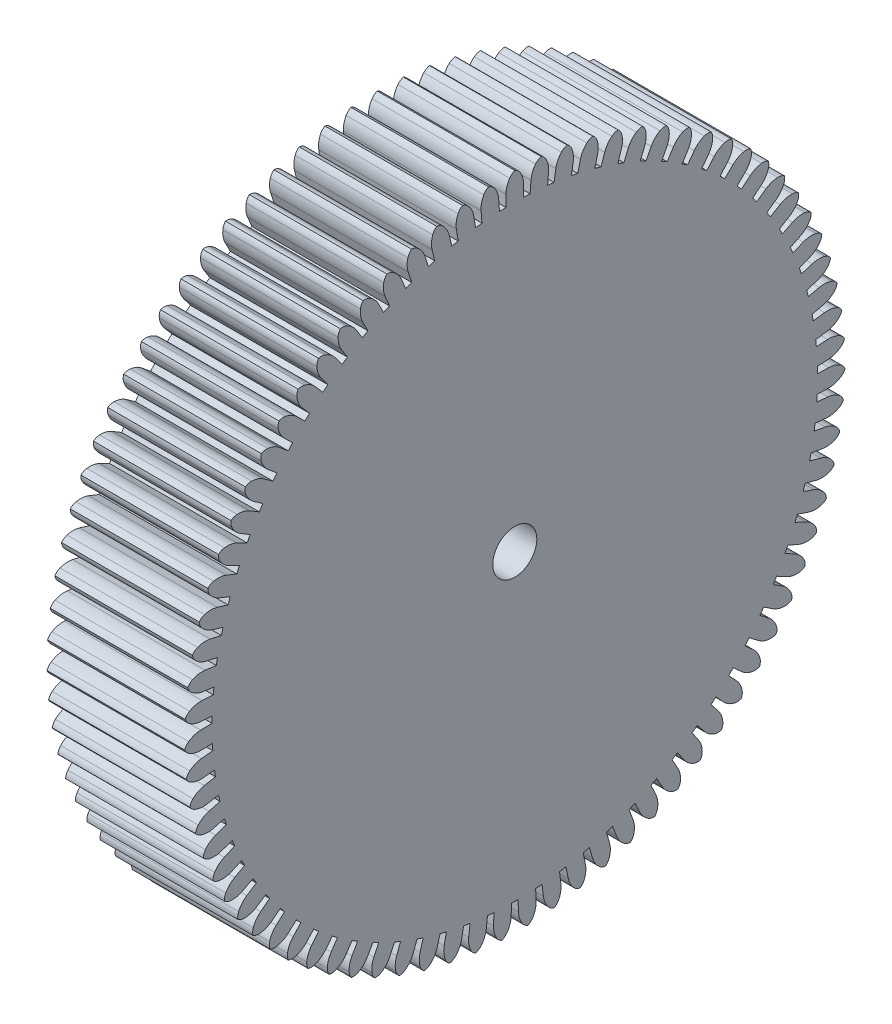
SolidWorks part; units mm, degrees
ref_plane "Front Plane" through (0, 0, 0) normal (0, 0, 1) x (1, 0, 0)
ref_plane "Top Plane" through (0, 0, 0) normal (0, 1, 0) x (1, 0, 0)
ref_plane "Right Plane" through (0, 0, 0) normal (1, 0, 0) x (0, 0, -1)
sketch "Sketch1" plane through (0, 0, 0) normal (1, 0, 0) x (0, 0, -1)
  line L0 (-0.64, 21.9907) -> (-0.64, 22.8144)
  line L1 (0, 24) -> (0, 22)
  line L2 (0, 55) -> (0, -55) construction
  line L3 (0.64, 21.9907) -> (0.64, 22.8144)
  line L4 (2.3851, 21.8703) -> (2.4506, 22.6915)
  line L5 (1.1092, 21.972) -> (1.1746, 22.7932)
  line L6 (4.1152, 21.6117) -> (4.2457, 22.425)
  line L7 (2.8514, 21.8144) -> (2.9818, 22.6278)
  line L8 (5.8192, 21.2164) -> (6.0139, 22.0168)
  line L9 (4.5755, 21.5189) -> (4.7702, 22.3193)
  line L10 (7.4865, 20.687) -> (7.7442, 21.4694)
  line L11 (6.2707, 21.0874) -> (6.5284, 21.8698)
  line L12 (9.1064, 20.0268) -> (9.4254, 20.7863)
  line L13 (7.9263, 20.5225) -> (8.2453, 21.282)
  line L14 (10.6688, 19.24) -> (11.0471, 19.9717)
  line L15 (9.5318, 19.8279) -> (9.9101, 20.5596)
  line L16 (12.1637, 18.3315) -> (12.5989, 19.0309)
  line L17 (11.077, 19.0079) -> (11.5122, 19.7073)
  line L18 (13.5817, 17.3072) -> (14.0711, 17.9697)
  line L19 (12.5521, 18.0678) -> (13.0416, 18.7303)
  line L20 (14.9138, 16.1734) -> (15.4543, 16.795)
  line L21 (13.9479, 17.0134) -> (14.4885, 17.6349)
  line L22 (16.1516, 14.9374) -> (16.7398, 15.514)
  line L23 (15.2556, 15.8514) -> (15.8438, 16.4281)
  line L24 (17.2873, 13.6069) -> (17.9195, 14.135)
  line L25 (16.4667, 14.5893) -> (17.0989, 15.1174)
  line L26 (18.3138, 12.1904) -> (18.9859, 12.6666)
  line L27 (17.5738, 13.2349) -> (18.2459, 13.7111)
  line L28 (19.2244, 10.6969) -> (19.9323, 11.1181)
  line L29 (18.5698, 11.7968) -> (19.2776, 12.2181)
  line L30 (20.0135, 9.1357) -> (20.7526, 9.4994)
  line L31 (19.4483, 10.2841) -> (20.1874, 10.6478)
  line L32 (20.6761, 7.5167) -> (21.4417, 7.8206)
  line L33 (20.2039, 8.7064) -> (20.9696, 9.0103)
  line L34 (21.2079, 5.8502) -> (21.9953, 6.0923)
  line L35 (20.8318, 7.0737) -> (21.6191, 7.3158)
  line L36 (21.6057, 4.1468) -> (22.4098, 4.3255)
  line L37 (21.3279, 5.3963) -> (22.132, 5.575)
  line L38 (21.8668, 2.4171) -> (22.6826, 2.5314)
  line L39 (21.6892, 3.6847) -> (22.505, 3.799)
  line L40 (21.9897, 0.6721) -> (22.812, 0.7212)
  line L41 (21.9134, 1.9498) -> (22.7357, 1.9989)
  line L42 (21.9736, -1.0771) -> (22.7972, -1.0935)
  line L43 (21.9991, 0.2027) -> (22.8226, 0.1863)
  line L44 (21.8186, -2.8195) -> (22.6383, -2.9013)
  line L45 (21.9456, -1.5458) -> (22.7653, -1.6276)
  line L46 (21.5256, -4.5441) -> (22.3362, -4.6907)
  line L47 (21.7534, -3.2845) -> (22.564, -3.4311)
  line L48 (21.0965, -6.2399) -> (21.8929, -6.4505)
  line L49 (21.4237, -5.0024) -> (22.2201, -5.213)
  line L50 (20.5341, -7.8963) -> (21.3112, -8.1695)
  line L51 (20.9585, -6.6888) -> (21.7357, -6.9619)
  line L52 (19.8418, -9.5028) -> (20.5948, -9.8368)
  line L53 (20.3609, -8.3328) -> (21.1138, -8.6668)
  line L54 (19.0241, -11.0492) -> (19.7481, -11.442)
  line L55 (19.6345, -9.9241) -> (20.3585, -10.3169)
  line L56 (18.0861, -12.5257) -> (18.7766, -12.9748)
  line L57 (18.7839, -11.4527) -> (19.4745, -11.9018)
  line L58 (17.0337, -13.9231) -> (17.6864, -14.4256)
  line L59 (17.8146, -12.9089) -> (18.4673, -13.4114)
  line L60 (15.8737, -15.2324) -> (16.4844, -15.7852)
  line L61 (16.7327, -14.2834) -> (17.3434, -14.8363)
  line L62 (14.6133, -16.4454) -> (15.1781, -17.045)
  line L63 (15.545, -15.5677) -> (16.1098, -16.1673)
  line L64 (13.2605, -17.5545) -> (13.7759, -18.197)
  line L65 (14.259, -16.7535) -> (14.7744, -17.3961)
  line L66 (11.8239, -18.5525) -> (12.2866, -19.234)
  line L67 (12.8828, -17.8335) -> (13.3456, -18.5149)
  line L68 (10.3125, -19.4333) -> (10.7196, -20.1494)
  line L69 (11.4252, -18.8006) -> (11.8324, -19.5167)
  line L70 (8.7359, -20.1912) -> (9.0849, -20.9374)
  line L71 (9.8954, -19.6489) -> (10.2444, -20.3951)
  line L72 (7.1041, -20.8214) -> (7.3927, -21.593)
  line L73 (8.303, -20.373) -> (8.5916, -21.1446)
  line L74 (5.4274, -21.32) -> (5.6538, -22.1121)
  line L75 (6.6581, -20.9683) -> (6.8845, -21.7603)
  line L76 (3.7164, -21.6838) -> (3.8791, -22.4913)
  line L77 (4.9712, -21.431) -> (5.1339, -22.2385)
  line L78 (1.9818, -21.9106) -> (2.0799, -22.7284)
  line L79 (3.2527, -21.7582) -> (3.3508, -22.5761)
  line L80 (0.2348, -21.9987) -> (0.2675, -22.8218)
  line L81 (1.5138, -21.9479) -> (1.5465, -22.771)
  line L82 (-1.5138, -21.9479) -> (-1.5465, -22.771)
  line L83 (-0.2348, -21.9987) -> (-0.2675, -22.8218)
  line L84 (-3.2527, -21.7582) -> (-3.3508, -22.5761)
  line L85 (-1.9818, -21.9106) -> (-2.0799, -22.7284)
  line L86 (-4.9712, -21.431) -> (-5.1339, -22.2385)
  line L87 (-3.7164, -21.6838) -> (-3.8791, -22.4913)
  line L88 (-6.6581, -20.9683) -> (-6.8845, -21.7603)
  line L89 (-5.4274, -21.32) -> (-5.6538, -22.1121)
  line L90 (-8.303, -20.373) -> (-8.5916, -21.1446)
  line L91 (-7.1041, -20.8214) -> (-7.3927, -21.593)
  line L92 (-9.8954, -19.6489) -> (-10.2444, -20.3951)
  line L93 (-8.7359, -20.1912) -> (-9.0849, -20.9374)
  line L94 (-11.4252, -18.8006) -> (-11.8324, -19.5167)
  line L95 (-10.3125, -19.4333) -> (-10.7196, -20.1494)
  line L96 (-12.8828, -17.8335) -> (-13.3456, -18.5149)
  line L97 (-11.8239, -18.5525) -> (-12.2866, -19.234)
  line L98 (-14.259, -16.7535) -> (-14.7744, -17.3961)
  line L99 (-13.2605, -17.5545) -> (-13.7759, -18.197)
  line L100 (-15.545, -15.5677) -> (-16.1098, -16.1673)
  line L101 (-14.6133, -16.4454) -> (-15.1781, -17.045)
  line L102 (-16.7327, -14.2834) -> (-17.3434, -14.8363)
  line L103 (-15.8737, -15.2324) -> (-16.4844, -15.7852)
  line L104 (-17.8146, -12.9089) -> (-18.4673, -13.4114)
  line L105 (-17.0337, -13.9231) -> (-17.6864, -14.4256)
  line L106 (-18.7839, -11.4527) -> (-19.4745, -11.9018)
  line L107 (-18.0861, -12.5257) -> (-18.7766, -12.9748)
  line L108 (-19.6345, -9.9241) -> (-20.3585, -10.3169)
  line L109 (-19.0241, -11.0492) -> (-19.7481, -11.442)
  line L110 (-20.3609, -8.3328) -> (-21.1138, -8.6668)
  line L111 (-19.8418, -9.5028) -> (-20.5948, -9.8368)
  line L112 (-20.9585, -6.6888) -> (-21.7357, -6.9619)
  line L113 (-20.5341, -7.8963) -> (-21.3112, -8.1695)
  line L114 (-21.4237, -5.0024) -> (-22.2201, -5.213)
  line L115 (-21.0965, -6.2399) -> (-21.8929, -6.4505)
  line L116 (-21.7534, -3.2845) -> (-22.564, -3.4311)
  line L117 (-21.5256, -4.5441) -> (-22.3362, -4.6907)
  line L118 (-21.9456, -1.5458) -> (-22.7653, -1.6276)
  line L119 (-21.8186, -2.8195) -> (-22.6383, -2.9013)
  line L120 (-21.9991, 0.2027) -> (-22.8226, 0.1863)
  line L121 (-21.9736, -1.0771) -> (-22.7972, -1.0935)
  line L122 (-21.9134, 1.9498) -> (-22.7357, 1.9989)
  line L123 (-21.9897, 0.6721) -> (-22.812, 0.7212)
  line L124 (-21.6892, 3.6847) -> (-22.505, 3.799)
  line L125 (-21.8668, 2.4171) -> (-22.6826, 2.5314)
  line L126 (-21.3279, 5.3963) -> (-22.132, 5.575)
  line L127 (-21.6057, 4.1468) -> (-22.4098, 4.3255)
  line L128 (-20.8318, 7.0737) -> (-21.6191, 7.3158)
  line L129 (-21.2079, 5.8502) -> (-21.9953, 6.0923)
  line L130 (-20.2039, 8.7064) -> (-20.9696, 9.0103)
  line L131 (-20.6761, 7.5167) -> (-21.4417, 7.8206)
  line L132 (-19.4483, 10.2841) -> (-20.1874, 10.6478)
  line L133 (-20.0135, 9.1357) -> (-20.7526, 9.4994)
  line L134 (-18.5698, 11.7968) -> (-19.2776, 12.2181)
  line L135 (-19.2244, 10.6969) -> (-19.9323, 11.1181)
  line L136 (-17.5738, 13.2349) -> (-18.2459, 13.7111)
  line L137 (-18.3138, 12.1904) -> (-18.9859, 12.6666)
  line L138 (-16.4667, 14.5893) -> (-17.0989, 15.1174)
  line L139 (-17.2873, 13.6069) -> (-17.9195, 14.135)
  line L140 (-15.2556, 15.8514) -> (-15.8438, 16.4281)
  line L141 (-16.1516, 14.9374) -> (-16.7398, 15.514)
  line L142 (-13.9479, 17.0134) -> (-14.4885, 17.6349)
  line L143 (-14.9138, 16.1734) -> (-15.4543, 16.795)
  line L144 (-12.5521, 18.0678) -> (-13.0416, 18.7303)
  line L145 (-13.5817, 17.3072) -> (-14.0711, 17.9697)
  line L146 (-11.077, 19.0079) -> (-11.5122, 19.7073)
  line L147 (-12.1637, 18.3315) -> (-12.5989, 19.0309)
  line L148 (-9.5318, 19.8279) -> (-9.9101, 20.5596)
  line L149 (-10.6688, 19.24) -> (-11.0471, 19.9717)
  line L150 (-7.9263, 20.5225) -> (-8.2453, 21.282)
  line L151 (-9.1064, 20.0268) -> (-9.4254, 20.7863)
  line L152 (-6.2707, 21.0874) -> (-6.5284, 21.8698)
  line L153 (-7.4865, 20.687) -> (-7.7442, 21.4694)
  line L154 (-4.5755, 21.5189) -> (-4.7702, 22.3193)
  line L155 (-5.8192, 21.2164) -> (-6.0139, 22.0168)
  line L156 (-2.8514, 21.8144) -> (-2.9818, 22.6278)
  line L157 (-4.1152, 21.6117) -> (-4.2457, 22.425)
  line L158 (-1.1092, 21.972) -> (-1.1746, 22.7932)
  line L159 (-2.3851, 21.8703) -> (-2.4506, 22.6915)
  circle A0 centre (0, 0) radius 1.6
  circle A1 centre (0, 0) radius 22
  arc A2 (-0.64, 22.8144) -> (-0.375, 23.6963) centre (0.96, 22.8144) cw
  arc A3 (-0.375, 23.6963) -> (0, 24) centre (0.2925, 23.2554) cw
  arc A4 (0.64, 22.8144) -> (0.375, 23.6963) centre (-0.96, 22.8144) ccw
  arc A5 (0.375, 23.6963) -> (0, 24) centre (-0.2925, 23.2554) ccw
  arc A6 (2.4506, 22.6915) -> (2.2565, 23.5916) centre (0.8556, 22.8186) ccw
  arc A7 (1.1746, 22.7932) -> (1.5089, 23.6512) centre (2.7696, 22.666) cw
  arc A8 (1.5089, 23.6512) -> (1.9068, 23.9241) centre (2.1392, 23.1586) cw
  arc A9 (2.2565, 23.5916) -> (1.9068, 23.9241) centre (1.5561, 23.2051) ccw
  arc A10 (4.2457, 22.425) -> (4.1237, 23.3378) centre (2.6659, 22.6785) ccw
  arc A11 (2.9818, 22.6278) -> (3.3832, 23.4566) centre (4.5616, 22.3743) cw
  arc A12 (3.3832, 23.4566) -> (3.8016, 23.697) centre (3.9724, 22.9155) cw
  arc A13 (4.1237, 23.3378) -> (3.8016, 23.697) centre (3.3948, 23.0081) ccw
  arc A14 (6.0139, 22.0168) -> (5.9649, 22.9364) centre (4.4593, 22.395) ccw
  arc A15 (4.7702, 22.3193) -> (5.2361, 23.1136) centre (6.3249, 21.9412) cw
  arc A16 (5.2361, 23.1136) -> (5.6723, 23.3201) centre (5.7805, 22.5274) cw
  arc A17 (5.9649, 22.9364) -> (5.6723, 23.3201) centre (5.2121, 22.6657) ccw
  arc A18 (7.7442, 21.4694) -> (7.7683, 22.39) centre (6.2244, 21.9699) ccw
  arc A19 (6.5284, 21.8698) -> (7.056, 22.6246) centre (8.0481, 21.3693) cw
  arc A20 (7.056, 22.6246) -> (7.5071, 22.7957) centre (7.552, 21.9969) cw
  arc A21 (7.7683, 22.39) -> (7.5071, 22.7957) centre (6.9964, 22.1799) ccw
  arc A22 (9.4254, 20.7863) -> (9.5226, 21.702) centre (7.9503, 21.4059) ccw
  arc A23 (8.2453, 21.282) -> (8.8312, 21.9925) centre (9.7205, 20.6623) cw
  arc A24 (8.8312, 21.9925) -> (9.2945, 22.1272) centre (9.2758, 21.3274) cw
  arc A25 (9.5226, 21.702) -> (9.2945, 22.1272) centre (8.7365, 21.554) ccw
  arc A26 (11.0471, 19.9717) -> (11.2168, 20.8768) centre (9.6259, 20.7066) ccw
  arc A27 (9.9101, 20.5596) -> (10.5506, 21.2213) centre (11.3314, 19.8247) cw
  arc A28 (10.5506, 21.2213) -> (11.0231, 21.3188) centre (10.941, 20.523) cw
  arc A29 (11.2168, 20.8768) -> (11.0231, 21.3188) centre (10.4213, 20.7917) ccw
  arc A30 (12.5989, 19.0309) -> (12.84, 19.9196) centre (11.2406, 19.8764) ccw
  arc A31 (11.5122, 19.7073) -> (12.2032, 20.316) centre (12.8706, 18.8618) cw
  arc A32 (12.2032, 20.316) -> (12.6821, 20.3756) centre (12.5369, 19.5889) cw
  arc A33 (12.84, 19.9196) -> (12.6821, 20.3756) centre (12.0403, 19.898) ccw
  arc A34 (14.0711, 17.9697) -> (14.382, 18.8365) centre (12.7842, 18.9205) ccw
  arc A35 (13.0416, 18.7303) -> (13.7788, 19.2822) centre (14.3285, 17.7796) cw
  arc A36 (13.7788, 19.2822) -> (14.2608, 19.3036) centre (14.0536, 18.5309) cw
  arc A37 (14.382, 18.8365) -> (14.2608, 19.3036) centre (13.5831, 18.8785) ccw
  arc A38 (15.4543, 16.795) -> (15.8331, 17.6343) centre (14.247, 17.8449) ccw
  arc A39 (14.4885, 17.6349) -> (15.2672, 18.1265) centre (15.6958, 16.585) cw
  arc A40 (15.2672, 18.1265) -> (15.7494, 18.1096) centre (15.4815, 17.3557) cw
  arc A41 (15.8331, 17.6343) -> (15.7494, 18.1096) centre (15.0401, 17.7396) ccw
  arc A42 (16.7398, 15.514) -> (17.1841, 16.3207) centre (15.6198, 16.6566) ccw
  arc A43 (15.8438, 16.4281) -> (16.6591, 16.8562) centre (16.9639, 15.2855) cw
  arc A44 (16.6591, 16.8562) -> (17.1384, 16.801) centre (16.8115, 16.0709) cw
  arc A45 (17.1841, 16.3207) -> (17.1384, 16.801) centre (16.4019, 16.4886) ccw
  arc A46 (17.9195, 14.135) -> (18.4265, 14.9038) centre (16.8938, 15.363) ccw
  arc A47 (17.0989, 15.1174) -> (17.9457, 15.4794) centre (18.1247, 13.8894) cw
  arc A48 (17.9457, 15.4794) -> (18.4191, 15.3862) centre (18.0352, 14.6844) cw
  arc A49 (18.4265, 14.9038) -> (18.4191, 15.3862) centre (17.6601, 15.1334) ccw
  arc A50 (18.9859, 12.6666) -> (19.5523, 13.3927) centre (18.061, 13.9722) ccw
  arc A51 (18.2459, 13.7111) -> (19.1188, 14.0047) centre (19.1709, 12.4055) cw
  arc A52 (19.1188, 14.0047) -> (19.5833, 13.8742) centre (19.1448, 13.2051) cw
  arc A53 (19.5523, 13.3927) -> (19.5833, 13.8742) centre (18.8066, 13.6824) ccw
  arc A54 (19.9323, 11.1181) -> (20.5546, 11.7969) centre (19.114, 12.4931) ccw
  arc A55 (19.2776, 12.2181) -> (20.171, 12.4414) centre (20.0959, 10.8432) cw
  arc A56 (20.171, 12.4414) -> (20.6237, 12.2745) centre (20.1335, 11.6423) cw
  arc A57 (20.5546, 11.7969) -> (20.6237, 12.2745) centre (19.8343, 12.145) ccw
  arc A58 (20.7526, 9.4994) -> (21.4269, 10.1266) centre (20.0461, 10.935) ccw
  arc A59 (20.1874, 10.6478) -> (21.0957, 10.7995) centre (20.8939, 9.2123) cw
  arc A60 (21.0957, 10.7995) -> (21.5337, 10.5971) centre (20.9948, 10.0059) cw
  arc A61 (21.4269, 10.1266) -> (21.5337, 10.5971) centre (20.7365, 10.5308) ccw
  arc A62 (21.4417, 7.8206) -> (22.1637, 8.3922) centre (20.8515, 9.3077) ccw
  arc A63 (20.9696, 9.0103) -> (21.887, 9.0893) centre (21.5597, 7.5231) cw
  arc A64 (21.887, 9.0893) -> (22.3076, 8.8527) centre (21.7234, 8.3062) cw
  arc A65 (22.1637, 8.3922) -> (22.3076, 8.8527) centre (21.5076, 8.8499) ccw
  arc A66 (21.9953, 6.0923) -> (22.7604, 6.6047) centre (21.5251, 7.6216) ccw
  arc A67 (21.6191, 7.3158) -> (22.54, 7.3216) centre (22.0893, 5.7864) cw
  arc A68 (22.54, 7.3216) -> (22.9404, 7.0524) centre (22.3146, 6.554) cw
  arc A69 (22.7604, 6.6047) -> (22.9404, 7.0524) centre (22.1427, 7.1132) ccw
  arc A70 (22.4098, 4.3255) -> (23.2132, 4.7755) centre (22.0626, 5.8874) ccw
  arc A71 (22.132, 5.575) -> (23.0504, 5.5077) centre (22.4792, 4.0131) cw
  arc A72 (23.0504, 5.5077) -> (23.4282, 5.2075) centre (22.7648, 4.7604) cw
  arc A73 (23.2132, 4.7755) -> (23.4282, 5.2075) centre (22.6379, 5.3315) ccw
  arc A74 (22.6826, 2.5314) -> (23.5192, 2.9162) centre (22.4606, 4.1159) ccw
  arc A75 (22.505, 3.799) -> (23.4152, 3.6589) centre (22.727, 2.2145) cw
  arc A76 (23.4152, 3.6589) -> (23.7679, 3.3297) centre (23.0711, 2.9367) cw
  arc A77 (23.5192, 2.9162) -> (23.7679, 3.3297) centre (22.9899, 3.516) ccw
  arc A78 (22.812, 0.7212) -> (23.6766, 1.0383) centre (22.7166, 2.3184) ccw
  arc A79 (22.7357, 1.9989) -> (23.6318, 1.787) centre (22.8311, 0.4018) cw
  arc A80 (23.6318, 1.787) -> (23.9573, 1.4308) centre (23.2315, 1.0944) cw
  arc A81 (23.6766, 1.0383) -> (23.9573, 1.4308) centre (23.1966, 1.6784) ccw
  arc A82 (22.7972, -1.0935) -> (23.6842, -0.8461) centre (22.829, 0.5062) ccw
  arc A83 (22.8226, 0.1863) -> (23.6991, -0.0962) centre (22.7908, -1.4134) cw
  arc A84 (23.6991, -0.0962) -> (23.9953, -0.4772) centre (23.245, -0.7548) cw
  arc A85 (23.6842, -0.8461) -> (23.9953, -0.4772) centre (23.2566, -0.1699) ccw
  arc A86 (22.6383, -2.9013) -> (23.5421, -2.7251) centre (22.7971, -1.3092) ccw
  arc A87 (22.7653, -1.6276) -> (23.6166, -1.9788) centre (22.6065, -3.2197) cw
  arc A88 (23.6166, -1.9788) -> (23.8815, -2.3821) centre (23.1115, -2.5992) cw
  arc A89 (23.5421, -2.7251) -> (23.8815, -2.3821) centre (23.1696, -2.0171) ccw
  arc A90 (22.3362, -4.6907) -> (23.2512, -4.5869) centre (22.621, -3.1163) ccw
  arc A91 (22.564, -3.4311) -> (23.3847, -3.8489) centre (22.2792, -5.0056) cw
  arc A92 (23.3847, -3.8489) -> (23.6167, -4.2719) centre (22.832, -4.4272) cw
  arc A93 (23.2512, -4.5869) -> (23.6167, -4.2719) centre (22.9361, -3.8516) ccw
  arc A94 (21.8929, -6.4505) -> (22.8133, -6.4197) centre (22.3019, -4.9036) ccw
  arc A95 (22.2201, -5.213) -> (23.005, -5.6946) centre (21.8111, -6.7599) cw
  arc A96 (23.005, -5.6946) -> (23.2027, -6.1348) centre (22.408, -6.2272) cw
  arc A97 (22.8133, -6.4197) -> (23.2027, -6.1348) centre (22.5576, -5.6617) ccw
  arc A98 (21.3112, -8.1695) -> (22.2311, -8.2119) centre (21.8418, -6.66) ccw
  arc A99 (21.7357, -6.9619) -> (22.4798, -7.5044) centre (21.2051, -8.4714) cw
  arc A100 (22.4798, -7.5044) -> (22.6419, -7.9589) centre (21.8424, -7.9879) cw
  arc A101 (22.2311, -8.2119) -> (22.6419, -7.9589) centre (22.0364, -7.436) ccw
  arc A102 (20.5948, -9.8368) -> (21.5084, -9.9523) centre (21.2436, -8.3743) ccw
  arc A103 (21.1138, -8.6668) -> (21.8125, -9.2667) centre (20.465, -10.1294) cw
  arc A104 (21.8125, -9.2667) -> (21.938, -9.7326) centre (21.1388, -9.698) cw
  arc A105 (21.5084, -9.9523) -> (21.938, -9.7326) centre (21.376, -9.1633) ccw
  arc A106 (19.7481, -11.442) -> (20.6497, -11.6296) centre (20.5111, -10.0356) ccw
  arc A107 (20.3585, -10.3169) -> (21.0073, -10.9704) centre (19.5955, -11.7233) cw
  arc A108 (21.0073, -10.9704) -> (21.0954, -11.4448) centre (20.3014, -11.3468) cw
  arc A109 (20.6497, -11.6296) -> (21.0954, -11.4448) centre (20.5804, -10.8326) ccw
  arc A110 (18.7766, -12.9748) -> (19.6604, -13.2335) centre (19.6489, -11.6335) ccw
  arc A111 (19.4745, -11.9018) -> (20.0693, -12.6048) centre (18.6022, -13.2431) cw
  arc A112 (20.0693, -12.6048) -> (20.1194, -13.0847) centre (19.3357, -12.9239) cw
  arc A113 (19.6604, -13.2335) -> (20.1194, -13.0847) centre (19.6547, -12.4335) ccw
  arc A114 (17.6864, -14.4256) -> (18.5469, -14.7537) centre (18.6625, -13.1579) ccw
  arc A115 (18.4673, -13.4114) -> (19.0044, -14.1594) centre (17.4912, -14.6792) cw
  arc A116 (19.0044, -14.1594) -> (19.0162, -14.6418) centre (18.2478, -14.4193) cw
  arc A117 (18.5469, -14.7537) -> (19.0162, -14.6418) centre (18.6047, -13.9558) ccw
  arc A118 (16.4844, -15.7852) -> (17.3161, -16.1806) centre (17.5582, -14.599) ccw
  arc A119 (17.3434, -14.8363) -> (17.8194, -15.6246) centre (16.2696, -16.0224) cw
  arc A120 (17.8194, -15.6246) -> (17.7928, -16.1064) centre (17.0445, -15.8235) cw
  arc A121 (17.3161, -16.1806) -> (17.7928, -16.1064) centre (17.4371, -15.3898) ccw
  arc A122 (15.1781, -17.045) -> (15.9758, -17.5052) centre (16.3428, -15.9479) ccw
  arc A123 (16.1098, -16.1673) -> (16.5217, -16.9909) centre (14.9452, -17.2644) cw
  arc A124 (16.5217, -16.9909) -> (16.4569, -17.4691) centre (15.7335, -17.1277) cw
  arc A125 (15.9758, -17.5052) -> (16.4569, -17.4691) centre (16.1593, -16.7265) ccw
  arc A126 (13.7759, -18.197) -> (14.5345, -18.7191) centre (15.024, -17.1959) ccw
  arc A127 (14.7744, -17.3961) -> (15.1195, -18.2499) centre (13.5263, -18.3972) cw
  arc A128 (15.1195, -18.2499) -> (15.017, -18.7214) centre (14.3229, -18.3236) cw
  arc A129 (14.5345, -18.7191) -> (15.017, -18.7214) centre (14.7793, -17.9575) ccw
  arc A130 (12.2866, -19.234) -> (13.0013, -19.8147) centre (13.6103, -18.3352) ccw
  arc A131 (13.3456, -18.5149) -> (13.6218, -19.3934) centre (12.0219, -19.4138) cw
  arc A132 (13.6218, -19.3934) -> (13.4821, -19.8553) centre (12.8218, -19.4036) cw
  arc A133 (13.0013, -19.8147) -> (13.4821, -19.8553) centre (13.3058, -19.075) ccw
  arc A134 (10.7196, -20.1494) -> (11.3859, -20.7851) centre (12.1106, -19.3586) ccw
  arc A135 (11.8324, -19.5167) -> (12.0379, -20.4144) centre (10.4415, -20.3075) cw
  arc A136 (12.0379, -20.4144) -> (11.862, -20.8637) centre (11.2397, -20.361) cw
  arc A137 (11.3859, -20.7851) -> (11.862, -20.8637) centre (11.7482, -20.0718) ccw
  arc A138 (9.0849, -20.9374) -> (9.6985, -21.624) centre (10.5342, -20.2596) ccw
  arc A139 (10.2444, -20.3951) -> (10.3779, -21.3063) centre (8.795, -21.0729) cw
  arc A140 (10.3779, -21.3063) -> (10.1669, -21.7402) centre (9.5865, -21.1896) cw
  arc A141 (9.6985, -21.624) -> (10.1669, -21.7402) centre (10.1164, -20.9418) ccw
  arc A142 (7.3927, -21.593) -> (7.9499, -22.3262) centre (8.8913, -21.0325) ccw
  arc A143 (8.5916, -21.1446) -> (8.6523, -22.0634) centre (7.093, -21.7051) cw
  arc A144 (8.6523, -22.0634) -> (8.4075, -22.4792) centre (7.8727, -21.8842) cw
  arc A145 (7.9499, -22.3262) -> (8.4075, -22.4792) centre (8.4206, -21.6793) ccw
  arc A146 (5.6538, -22.1121) -> (6.1509, -22.8872) centre (7.1922, -21.6724) ccw
  arc A147 (6.8845, -21.7603) -> (6.872, -22.6811) centre (5.3461, -22.2) cw
  arc A148 (6.872, -22.6811) -> (6.5949, -23.0761) centre (6.1091, -22.4405) cw
  arc A149 (6.1509, -22.8872) -> (6.5949, -23.0761) centre (6.6715, -22.2798) ccw
  arc A150 (3.8791, -22.4913) -> (4.3131, -23.3035) centre (5.4476, -22.1753) ccw
  arc A151 (5.1339, -22.2385) -> (5.0483, -23.1554) centre (3.5654, -22.5546) cw
  arc A152 (5.0483, -23.1554) -> (4.7407, -23.5271) centre (4.3068, -22.855) cw
  arc A153 (4.3131, -23.3035) -> (4.7407, -23.5271) centre (4.8803, -22.7394) ccw
  arc A154 (2.0799, -22.7284) -> (2.448, -23.5725) centre (3.6685, -22.538) ccw
  arc A155 (3.3508, -22.5761) -> (3.1926, -23.4833) centre (1.7622, -22.7665) cw
  arc A156 (3.1926, -23.4833) -> (2.8564, -23.8294) centre (2.4774, -23.1249) cw
  arc A157 (2.448, -23.5725) -> (2.8564, -23.8294) centre (3.0582, -23.0553) ccw
  arc A158 (0.2675, -22.8218) -> (0.5674, -23.6925) centre (1.8663, -22.7582) ccw
  arc A159 (1.5465, -22.771) -> (1.3168, -23.6627) centre (-0.0522, -22.8346) cw
  arc A160 (1.3168, -23.6627) -> (0.9542, -23.981) centre (0.6323, -23.2486) cw
  arc A161 (0.5674, -23.6925) -> (0.9542, -23.981) centre (1.2168, -23.2254) ccw
  arc A162 (-1.5465, -22.771) -> (-1.3168, -23.6627) centre (0.0522, -22.8346) ccw
  arc A163 (-0.2675, -22.8218) -> (-0.5674, -23.6925) centre (-1.8663, -22.7582) cw
  arc A164 (-0.5674, -23.6925) -> (-0.9542, -23.981) centre (-1.2168, -23.2254) cw
  arc A165 (-1.3168, -23.6627) -> (-0.9542, -23.981) centre (-0.6323, -23.2486) ccw
  arc A166 (-3.3508, -22.5761) -> (-3.1926, -23.4833) centre (-1.7622, -22.7665) ccw
  arc A167 (-2.0799, -22.7284) -> (-2.448, -23.5725) centre (-3.6685, -22.538) cw
  arc A168 (-2.448, -23.5725) -> (-2.8564, -23.8294) centre (-3.0582, -23.0553) cw
  arc A169 (-3.1926, -23.4833) -> (-2.8564, -23.8294) centre (-2.4774, -23.1249) ccw
  arc A170 (-5.1339, -22.2385) -> (-5.0483, -23.1554) centre (-3.5654, -22.5546) ccw
  arc A171 (-3.8791, -22.4913) -> (-4.3131, -23.3035) centre (-5.4476, -22.1753) cw
  arc A172 (-4.3131, -23.3035) -> (-4.7407, -23.5271) centre (-4.8803, -22.7394) cw
  arc A173 (-5.0483, -23.1554) -> (-4.7407, -23.5271) centre (-4.3068, -22.855) ccw
  arc A174 (-6.8845, -21.7603) -> (-6.872, -22.6811) centre (-5.3461, -22.2) ccw
  arc A175 (-5.6538, -22.1121) -> (-6.1509, -22.8872) centre (-7.1922, -21.6724) cw
  arc A176 (-6.1509, -22.8872) -> (-6.5949, -23.0761) centre (-6.6715, -22.2798) cw
  arc A177 (-6.872, -22.6811) -> (-6.5949, -23.0761) centre (-6.1091, -22.4405) ccw
  arc A178 (-8.5916, -21.1446) -> (-8.6523, -22.0634) centre (-7.093, -21.7051) ccw
  arc A179 (-7.3927, -21.593) -> (-7.9499, -22.3262) centre (-8.8913, -21.0325) cw
  arc A180 (-7.9499, -22.3262) -> (-8.4075, -22.4792) centre (-8.4206, -21.6793) cw
  arc A181 (-8.6523, -22.0634) -> (-8.4075, -22.4792) centre (-7.8727, -21.8842) ccw
  arc A182 (-10.2444, -20.3951) -> (-10.3779, -21.3063) centre (-8.795, -21.0729) ccw
  arc A183 (-9.0849, -20.9374) -> (-9.6985, -21.624) centre (-10.5342, -20.2596) cw
  arc A184 (-9.6985, -21.624) -> (-10.1669, -21.7402) centre (-10.1164, -20.9418) cw
  arc A185 (-10.3779, -21.3063) -> (-10.1669, -21.7402) centre (-9.5865, -21.1896) ccw
  arc A186 (-11.8324, -19.5167) -> (-12.0379, -20.4144) centre (-10.4415, -20.3075) ccw
  arc A187 (-10.7196, -20.1494) -> (-11.3859, -20.7851) centre (-12.1106, -19.3586) cw
  arc A188 (-11.3859, -20.7851) -> (-11.862, -20.8637) centre (-11.7482, -20.0718) cw
  arc A189 (-12.0379, -20.4144) -> (-11.862, -20.8637) centre (-11.2397, -20.361) ccw
  arc A190 (-13.3456, -18.5149) -> (-13.6218, -19.3934) centre (-12.0219, -19.4138) ccw
  arc A191 (-12.2866, -19.234) -> (-13.0013, -19.8147) centre (-13.6103, -18.3352) cw
  arc A192 (-13.0013, -19.8147) -> (-13.4821, -19.8553) centre (-13.3058, -19.075) cw
  arc A193 (-13.6218, -19.3934) -> (-13.4821, -19.8553) centre (-12.8218, -19.4036) ccw
  arc A194 (-14.7744, -17.3961) -> (-15.1195, -18.2499) centre (-13.5263, -18.3972) ccw
  arc A195 (-13.7759, -18.197) -> (-14.5345, -18.7191) centre (-15.024, -17.1959) cw
  arc A196 (-14.5345, -18.7191) -> (-15.017, -18.7214) centre (-14.7793, -17.9575) cw
  arc A197 (-15.1195, -18.2499) -> (-15.017, -18.7214) centre (-14.3229, -18.3236) ccw
  arc A198 (-16.1098, -16.1673) -> (-16.5217, -16.9909) centre (-14.9452, -17.2644) ccw
  arc A199 (-15.1781, -17.045) -> (-15.9758, -17.5052) centre (-16.3428, -15.9479) cw
  arc A200 (-15.9758, -17.5052) -> (-16.4569, -17.4691) centre (-16.1593, -16.7265) cw
  arc A201 (-16.5217, -16.9909) -> (-16.4569, -17.4691) centre (-15.7335, -17.1277) ccw
  arc A202 (-17.3434, -14.8363) -> (-17.8194, -15.6246) centre (-16.2696, -16.0224) ccw
  arc A203 (-16.4844, -15.7852) -> (-17.3161, -16.1806) centre (-17.5582, -14.599) cw
  arc A204 (-17.3161, -16.1806) -> (-17.7928, -16.1064) centre (-17.4371, -15.3898) cw
  arc A205 (-17.8194, -15.6246) -> (-17.7928, -16.1064) centre (-17.0445, -15.8235) ccw
  arc A206 (-18.4673, -13.4114) -> (-19.0044, -14.1594) centre (-17.4912, -14.6792) ccw
  arc A207 (-17.6864, -14.4256) -> (-18.5469, -14.7537) centre (-18.6625, -13.1579) cw
  arc A208 (-18.5469, -14.7537) -> (-19.0162, -14.6418) centre (-18.6047, -13.9558) cw
  arc A209 (-19.0044, -14.1594) -> (-19.0162, -14.6418) centre (-18.2478, -14.4193) ccw
  arc A210 (-19.4745, -11.9018) -> (-20.0693, -12.6048) centre (-18.6022, -13.2431) ccw
  arc A211 (-18.7766, -12.9748) -> (-19.6604, -13.2335) centre (-19.6489, -11.6335) cw
  arc A212 (-19.6604, -13.2335) -> (-20.1194, -13.0847) centre (-19.6547, -12.4335) cw
  arc A213 (-20.0693, -12.6048) -> (-20.1194, -13.0847) centre (-19.3357, -12.9239) ccw
  arc A214 (-20.3585, -10.3169) -> (-21.0073, -10.9704) centre (-19.5955, -11.7233) ccw
  arc A215 (-19.7481, -11.442) -> (-20.6497, -11.6296) centre (-20.5111, -10.0356) cw
  arc A216 (-20.6497, -11.6296) -> (-21.0954, -11.4448) centre (-20.5804, -10.8326) cw
  arc A217 (-21.0073, -10.9704) -> (-21.0954, -11.4448) centre (-20.3014, -11.3468) ccw
  arc A218 (-21.1138, -8.6668) -> (-21.8125, -9.2667) centre (-20.465, -10.1294) ccw
  arc A219 (-20.5948, -9.8368) -> (-21.5084, -9.9523) centre (-21.2436, -8.3743) cw
  arc A220 (-21.5084, -9.9523) -> (-21.938, -9.7326) centre (-21.376, -9.1633) cw
  arc A221 (-21.8125, -9.2667) -> (-21.938, -9.7326) centre (-21.1388, -9.698) ccw
  arc A222 (-21.7357, -6.9619) -> (-22.4798, -7.5044) centre (-21.2051, -8.4714) ccw
  arc A223 (-21.3112, -8.1695) -> (-22.2311, -8.2119) centre (-21.8418, -6.66) cw
  arc A224 (-22.2311, -8.2119) -> (-22.6419, -7.9589) centre (-22.0364, -7.436) cw
  arc A225 (-22.4798, -7.5044) -> (-22.6419, -7.9589) centre (-21.8424, -7.9879) ccw
  arc A226 (-22.2201, -5.213) -> (-23.005, -5.6946) centre (-21.8111, -6.7599) ccw
  arc A227 (-21.8929, -6.4505) -> (-22.8133, -6.4197) centre (-22.3019, -4.9036) cw
  arc A228 (-22.8133, -6.4197) -> (-23.2027, -6.1348) centre (-22.5576, -5.6617) cw
  arc A229 (-23.005, -5.6946) -> (-23.2027, -6.1348) centre (-22.408, -6.2272) ccw
  arc A230 (-22.564, -3.4311) -> (-23.3847, -3.8489) centre (-22.2792, -5.0056) ccw
  arc A231 (-22.3362, -4.6907) -> (-23.2512, -4.5869) centre (-22.621, -3.1163) cw
  arc A232 (-23.2512, -4.5869) -> (-23.6167, -4.2719) centre (-22.9361, -3.8516) cw
  arc A233 (-23.3847, -3.8489) -> (-23.6167, -4.2719) centre (-22.832, -4.4272) ccw
  arc A234 (-22.7653, -1.6276) -> (-23.6166, -1.9788) centre (-22.6065, -3.2197) ccw
  arc A235 (-22.6383, -2.9013) -> (-23.5421, -2.7251) centre (-22.7971, -1.3092) cw
  arc A236 (-23.5421, -2.7251) -> (-23.8815, -2.3821) centre (-23.1696, -2.0171) cw
  arc A237 (-23.6166, -1.9788) -> (-23.8815, -2.3821) centre (-23.1115, -2.5992) ccw
  arc A238 (-22.8226, 0.1863) -> (-23.6991, -0.0962) centre (-22.7908, -1.4134) ccw
  arc A239 (-22.7972, -1.0935) -> (-23.6842, -0.8461) centre (-22.829, 0.5062) cw
  arc A240 (-23.6842, -0.8461) -> (-23.9953, -0.4772) centre (-23.2566, -0.1699) cw
  arc A241 (-23.6991, -0.0962) -> (-23.9953, -0.4772) centre (-23.245, -0.7548) ccw
  arc A242 (-22.7357, 1.9989) -> (-23.6318, 1.787) centre (-22.8311, 0.4018) ccw
  arc A243 (-22.812, 0.7212) -> (-23.6766, 1.0383) centre (-22.7166, 2.3184) cw
  arc A244 (-23.6766, 1.0383) -> (-23.9573, 1.4308) centre (-23.1966, 1.6784) cw
  arc A245 (-23.6318, 1.787) -> (-23.9573, 1.4308) centre (-23.2315, 1.0944) ccw
  arc A246 (-22.505, 3.799) -> (-23.4152, 3.6589) centre (-22.727, 2.2145) ccw
  arc A247 (-22.6826, 2.5314) -> (-23.5192, 2.9162) centre (-22.4606, 4.1159) cw
  arc A248 (-23.5192, 2.9162) -> (-23.7679, 3.3297) centre (-22.9899, 3.516) cw
  arc A249 (-23.4152, 3.6589) -> (-23.7679, 3.3297) centre (-23.0711, 2.9367) ccw
  arc A250 (-22.132, 5.575) -> (-23.0504, 5.5077) centre (-22.4792, 4.0131) ccw
  arc A251 (-22.4098, 4.3255) -> (-23.2132, 4.7755) centre (-22.0626, 5.8874) cw
  arc A252 (-23.2132, 4.7755) -> (-23.4282, 5.2075) centre (-22.6379, 5.3315) cw
  arc A253 (-23.0504, 5.5077) -> (-23.4282, 5.2075) centre (-22.7648, 4.7604) ccw
  arc A254 (-21.6191, 7.3158) -> (-22.54, 7.3216) centre (-22.0893, 5.7864) ccw
  arc A255 (-21.9953, 6.0923) -> (-22.7604, 6.6047) centre (-21.5251, 7.6216) cw
  arc A256 (-22.7604, 6.6047) -> (-22.9404, 7.0524) centre (-22.1427, 7.1132) cw
  arc A257 (-22.54, 7.3216) -> (-22.9404, 7.0524) centre (-22.3146, 6.554) ccw
  arc A258 (-20.9696, 9.0103) -> (-21.887, 9.0893) centre (-21.5597, 7.5231) ccw
  arc A259 (-21.4417, 7.8206) -> (-22.1637, 8.3922) centre (-20.8515, 9.3077) cw
  arc A260 (-22.1637, 8.3922) -> (-22.3076, 8.8527) centre (-21.5076, 8.8499) cw
  arc A261 (-21.887, 9.0893) -> (-22.3076, 8.8527) centre (-21.7234, 8.3062) ccw
  arc A262 (-20.1874, 10.6478) -> (-21.0957, 10.7995) centre (-20.8939, 9.2123) ccw
  arc A263 (-20.7526, 9.4994) -> (-21.4269, 10.1266) centre (-20.0461, 10.935) cw
  arc A264 (-21.4269, 10.1266) -> (-21.5337, 10.5971) centre (-20.7365, 10.5308) cw
  arc A265 (-21.0957, 10.7995) -> (-21.5337, 10.5971) centre (-20.9948, 10.0059) ccw
  arc A266 (-19.2776, 12.2181) -> (-20.171, 12.4414) centre (-20.0959, 10.8432) ccw
  arc A267 (-19.9323, 11.1181) -> (-20.5546, 11.7969) centre (-19.114, 12.4931) cw
  arc A268 (-20.5546, 11.7969) -> (-20.6237, 12.2745) centre (-19.8343, 12.145) cw
  arc A269 (-20.171, 12.4414) -> (-20.6237, 12.2745) centre (-20.1335, 11.6423) ccw
  arc A270 (-18.2459, 13.7111) -> (-19.1188, 14.0047) centre (-19.1709, 12.4055) ccw
  arc A271 (-18.9859, 12.6666) -> (-19.5523, 13.3927) centre (-18.061, 13.9722) cw
  arc A272 (-19.5523, 13.3927) -> (-19.5833, 13.8742) centre (-18.8066, 13.6824) cw
  arc A273 (-19.1188, 14.0047) -> (-19.5833, 13.8742) centre (-19.1448, 13.2051) ccw
  arc A274 (-17.0989, 15.1174) -> (-17.9457, 15.4794) centre (-18.1247, 13.8894) ccw
  arc A275 (-17.9195, 14.135) -> (-18.4265, 14.9038) centre (-16.8938, 15.363) cw
  arc A276 (-18.4265, 14.9038) -> (-18.4191, 15.3862) centre (-17.6601, 15.1334) cw
  arc A277 (-17.9457, 15.4794) -> (-18.4191, 15.3862) centre (-18.0352, 14.6844) ccw
  arc A278 (-15.8438, 16.4281) -> (-16.6591, 16.8562) centre (-16.9639, 15.2855) ccw
  arc A279 (-16.7398, 15.514) -> (-17.1841, 16.3207) centre (-15.6198, 16.6566) cw
  arc A280 (-17.1841, 16.3207) -> (-17.1384, 16.801) centre (-16.4019, 16.4886) cw
  arc A281 (-16.6591, 16.8562) -> (-17.1384, 16.801) centre (-16.8115, 16.0709) ccw
  arc A282 (-14.4885, 17.6349) -> (-15.2672, 18.1265) centre (-15.6958, 16.585) ccw
  arc A283 (-15.4543, 16.795) -> (-15.8331, 17.6343) centre (-14.247, 17.8449) cw
  arc A284 (-15.8331, 17.6343) -> (-15.7494, 18.1096) centre (-15.0401, 17.7396) cw
  arc A285 (-15.2672, 18.1265) -> (-15.7494, 18.1096) centre (-15.4815, 17.3557) ccw
  arc A286 (-13.0416, 18.7303) -> (-13.7788, 19.2822) centre (-14.3285, 17.7796) ccw
  arc A287 (-14.0711, 17.9697) -> (-14.382, 18.8365) centre (-12.7842, 18.9205) cw
  arc A288 (-14.382, 18.8365) -> (-14.2608, 19.3036) centre (-13.5831, 18.8785) cw
  arc A289 (-13.7788, 19.2822) -> (-14.2608, 19.3036) centre (-14.0536, 18.5309) ccw
  arc A290 (-11.5122, 19.7073) -> (-12.2032, 20.316) centre (-12.8706, 18.8618) ccw
  arc A291 (-12.5989, 19.0309) -> (-12.84, 19.9196) centre (-11.2406, 19.8764) cw
  arc A292 (-12.84, 19.9196) -> (-12.6821, 20.3756) centre (-12.0403, 19.898) cw
  arc A293 (-12.2032, 20.316) -> (-12.6821, 20.3756) centre (-12.5369, 19.5889) ccw
  arc A294 (-9.9101, 20.5596) -> (-10.5506, 21.2213) centre (-11.3314, 19.8247) ccw
  arc A295 (-11.0471, 19.9717) -> (-11.2168, 20.8768) centre (-9.6259, 20.7066) cw
  arc A296 (-11.2168, 20.8768) -> (-11.0231, 21.3188) centre (-10.4213, 20.7917) cw
  arc A297 (-10.5506, 21.2213) -> (-11.0231, 21.3188) centre (-10.941, 20.523) ccw
  arc A298 (-8.2453, 21.282) -> (-8.8312, 21.9925) centre (-9.7205, 20.6623) ccw
  arc A299 (-9.4254, 20.7863) -> (-9.5226, 21.702) centre (-7.9503, 21.4059) cw
  arc A300 (-9.5226, 21.702) -> (-9.2945, 22.1272) centre (-8.7365, 21.554) cw
  arc A301 (-8.8312, 21.9925) -> (-9.2945, 22.1272) centre (-9.2758, 21.3274) ccw
  arc A302 (-6.5284, 21.8698) -> (-7.056, 22.6246) centre (-8.0481, 21.3693) ccw
  arc A303 (-7.7442, 21.4694) -> (-7.7683, 22.39) centre (-6.2244, 21.9699) cw
  arc A304 (-7.7683, 22.39) -> (-7.5071, 22.7957) centre (-6.9964, 22.1799) cw
  arc A305 (-7.056, 22.6246) -> (-7.5071, 22.7957) centre (-7.552, 21.9969) ccw
  arc A306 (-4.7702, 22.3193) -> (-5.2361, 23.1136) centre (-6.3249, 21.9412) ccw
  arc A307 (-6.0139, 22.0168) -> (-5.9649, 22.9364) centre (-4.4593, 22.395) cw
  arc A308 (-5.9649, 22.9364) -> (-5.6723, 23.3201) centre (-5.2121, 22.6657) cw
  arc A309 (-5.2361, 23.1136) -> (-5.6723, 23.3201) centre (-5.7805, 22.5274) ccw
  arc A310 (-2.9818, 22.6278) -> (-3.3832, 23.4566) centre (-4.5616, 22.3743) ccw
  arc A311 (-4.2457, 22.425) -> (-4.1237, 23.3378) centre (-2.6659, 22.6785) cw
  arc A312 (-4.1237, 23.3378) -> (-3.8016, 23.697) centre (-3.3948, 23.0081) cw
  arc A313 (-3.3832, 23.4566) -> (-3.8016, 23.697) centre (-3.9724, 22.9155) ccw
  arc A314 (-1.1746, 22.7932) -> (-1.5089, 23.6512) centre (-2.7696, 22.666) ccw
  arc A315 (-2.4506, 22.6915) -> (-2.2565, 23.5916) centre (-0.8556, 22.8186) cw
  arc A316 (-2.2565, 23.5916) -> (-1.9068, 23.9241) centre (-1.5561, 23.2051) cw
  arc A317 (-1.5089, 23.6512) -> (-1.9068, 23.9241) centre (-2.1392, 23.1586) ccw
  point P318 (0, 0)
  dimension "D1" = 3.2
  dimension "D2" = 44
  dimension "D6" = 1.6
  dimension "D7" = 0.8
  dimension "D4" = 2
  dimension "D5" = 1.28
  dimension "D8" = 0.75
  dimension "D3" = 79
extrude "Boss-Extrude1" add sketch "Sketch1" along normal blind 10 contours A1 A0 | A66 A69 A68 A67 L35 A1 L34 | A70 A73 A72 A71 L37 A1 L36 | A6 A9 A8 A7 L5 A1 L4 | A10 A13 A12 A11 L7 A1 L6 | A14 A17 A16 A15 L9 A1 L8 | A18 A21 A20 A19 L11 A1 L10 | A22 A25 A24 A23 L13 A1 L12 | A26 A29 A28 A27 L15 A1 L14 | A30 A33 A32 A31 L17 A1 L16 | A34 A37 A36 A35 L19 A1 L18 | A38 A41 A40 A39 L21 A1 L20 | A42 A45 A44 A43 L23 A1 L22 | A46 A49 A48 A47 L25 A1 L24 | A50 A53 A52 A51 L27 A1 L26 | A54 A57 A56 A55 L29 A1 L28 | A58 A61 A60 A59 L31 A1 L30 | A62 A65 A64 A63 L33 A1 L32 | A3 A2 L0 A1 L1 | A4 A5 L1 A1 L3 | A142 A145 A144 A143 L73 A1 L72 | A138 A141 A140 A139 L71 A1 L70 | A134 A137 A136 A135 L69 A1 L68 | A130 A133 A132 A131 L67 A1 L66 | A126 A129 A128 A127 L65 A1 L64 | A122 A125 A124 A123 L63 A1 L62 | A114 A117 A116 A115 L59 A1 L58 | A118 A121 A120 A119 L61 A1 L60 | A110 A113 A112 A111 L57 A1 L56 | A106 A109 A108 A107 L55 A1 L54 | A102 A105 A104 A103 L53 A1 L52 | A98 A101 A100 A99 L51 A1 L50 | A94 A97 A96 A95 L49 A1 L48 | A90 A93 A92 A91 L47 A1 L46 | A86 A89 A88 A87 L45 A1 L44 | A82 A85 A84 A83 L43 A1 L42 | A78 A81 A80 A79 L41 A1 L40 | A74 A77 A76 A75 L39 A1 L38 | A314 A317 A316 A315 L159 A1 L158 | A310 A313 A312 A311 L157 A1 L156 | A306 A309 A308 A307 L155 A1 L154 | A302 A305 A304 A303 L153 A1 L152 | A298 A301 A300 A299 L151 A1 L150 | A294 A297 A296 A295 L149 A1 L148 | A290 A293 A292 A291 L147 A1 L146 | A286 A289 A288 A287 L145 A1 L144 | A282 A285 A284 A283 L143 A1 L142 | A278 A281 A280 A279 L141 A1 L140 | A274 A277 A276 A275 L139 A1 L138 | A270 A273 A272 A271 L137 A1 L136 | A266 A269 A268 A267 L135 A1 L134 | A262 A265 A264 A263 L133 A1 L132 | A258 A261 A260 A259 L131 A1 L130 | A254 A257 A256 A255 L129 A1 L128 | A250 A253 A252 A251 L127 A1 L126 | A246 A249 A248 A247 L125 A1 L124 | A242 A245 A244 A243 L123 A1 L122 | A238 A241 A240 A239 L121 A1 L120 | A234 A237 A236 A235 L119 A1 L118 | A230 A233 A232 A231 L117 A1 L116 | A226 A229 A228 A227 L115 A1 L114 | A222 A225 A224 A223 L113 A1 L112 | A218 A221 A220 A219 L111 A1 L110 | A214 A217 A216 A215 L109 A1 L108 | A210 A213 A212 A211 L107 A1 L106 | A206 A209 A208 A207 L105 A1 L104 | A202 A205 A204 A203 L103 A1 L102 | A198 A201 A200 A199 L101 A1 L100 | A194 A197 A196 A195 L99 A1 L98 | A190 A193 A192 A191 L97 A1 L96 | A186 A189 A188 A187 L95 A1 L94 | A182 A185 A184 A183 L93 A1 L92 | A178 A181 A180 A179 L91 A1 L90 | A174 A177 A176 A175 L89 A1 L88 | A170 A173 A172 A171 L87 A1 L86 | A166 A169 A168 A167 L85 A1 L84 | A162 A165 A164 A163 L83 A1 L82 | A158 A161 A160 A159 L81 A1 L80 | A154 A157 A156 A155 L79 A1 L78 | A150 A153 A152 A151 L77 A1 L76 | A146 A149 A148 A147 L75 A1 L74 region at (0, 22.864, 0.2919) region at (0, 21.3755, 0.311) region at (0, 22.864, -0.2919) region at (0, 22.7917, 1.8165) region at (0, 22.7917, -1.8165) region at (0, 22.5753, 3.6216) region at (0, 22.5753, -3.6216) region at (0, 22.2162, 5.4038) region at (0, 22.2162, -5.4038) region at (0, 21.7167, 7.1518) region at (0, 21.7167, -7.1518) region at (0, 21.0798, 8.8546) region at (0, 21.0798, -8.8546) region at (0, 20.3097, 10.5014) region at (0, 20.3097, -10.5014) region at (0, 19.4111, 12.0818) region at (0, 19.4111, -12.0818) region at (0, 18.3899, 13.5858) region at (0, 18.3899, -13.5858) region at (0, 17.2524, 15.0039) region at (0, 17.2524, -15.0039) region at (0, 16.0058, 16.3272) region at (0, 16.0058, -16.3272) region at (0, 14.658, 17.5473) region at (0, 14.658, -17.5473) region at (0, 13.2175, 18.6564) region at (0, 13.2175, -18.6564) region at (0, 11.6935, 19.6475) region at (0, 11.6935, -19.6475) region at (0, 10.0955, 20.5145) region at (0, 10.0955, -20.5145) region at (0, 8.4337, 21.2517) region at (0, 8.4337, -21.2517) region at (0, 6.7186, 21.8546) region at (0, 6.7186, -21.8546) region at (0, 4.961, 22.3193) region at (0, 4.961, -22.3193) region at (0, 3.172, 22.6429) region at (0, 3.172, -22.6429) region at (0, 1.363, 22.8233) region at (0, 1.363, -22.8233) region at (0, -0.4546, 22.8595) region at (0, -0.4546, -22.8595) region at (0, -2.2693, 22.7511) region at (0, -4.0697, 22.4989) region at (0, -2.2693, -22.7511) region at (0, -5.8444, 22.1044) region at (0, -4.0697, -22.4989) region at (0, -7.5821, 21.5702) region at (0, -5.8444, -22.1044) region at (0, -9.2719, 20.8996) region at (0, -7.5821, -21.5702) region at (0, -10.9031, 20.0969) region at (0, -9.2719, -20.8996) region at (0, -12.4653, 19.1671) region at (0, -10.9031, -20.0969) region at (0, -13.9487, 18.1161) region at (0, -12.4653, -19.1671) region at (0, -15.344, 16.9506) region at (0, -13.9487, -18.1161)
